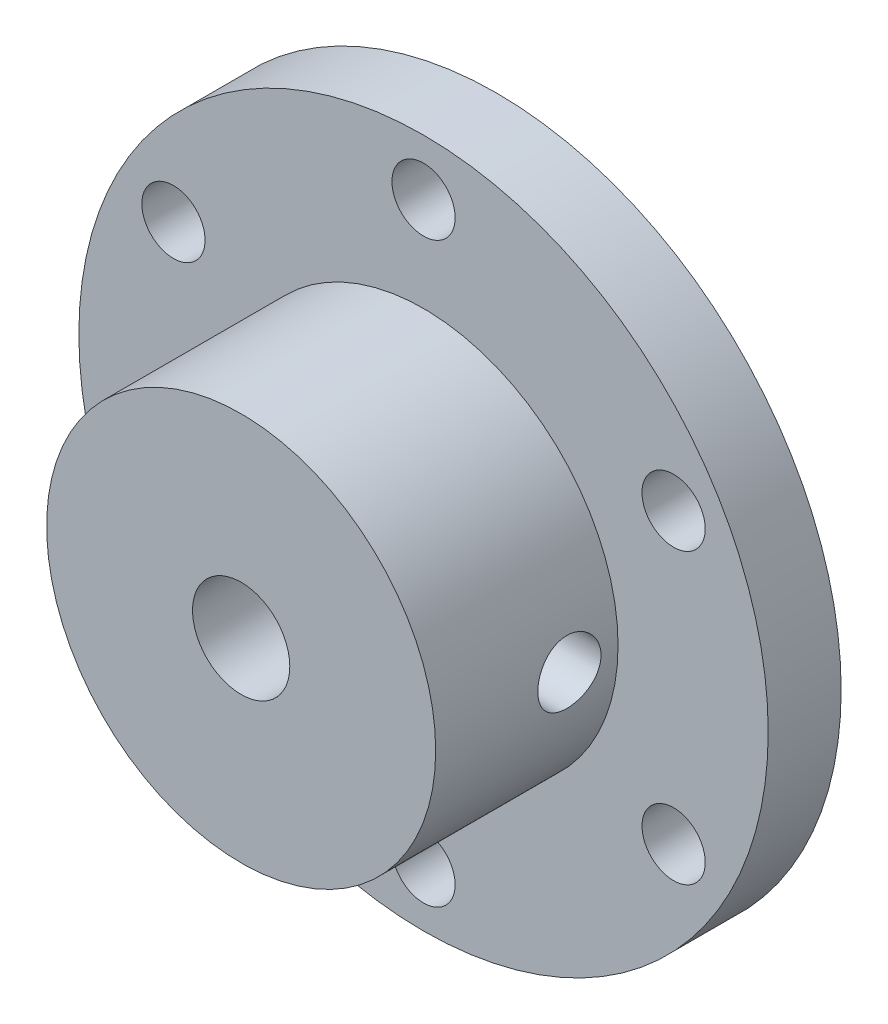
SolidWorks part; units mm, degrees
material "6061 合金"
ref_plane "前基準面" through (0, 0, 0) normal (0, 0, 1) x (1, 0, 0)
ref_plane "上基準面" through (0, 0, 0) normal (0, 1, 0) x (1, 0, 0)
ref_plane "右基準面" through (0, 0, 0) normal (1, 0, 0) x (0, 0, -1)
sketch "草圖1" plane through (0, 0, 0) normal (0, 0, 1) x (1, 0, 0)
  circle A0 centre (0, 0) radius 28.35
  dimension "D1" = 56.7
extrude "填料-伸長1" add sketch "草圖1" along normal blind 6
sketch "草圖2" plane through (0, 0, 6) normal (0, 0, 1) x (1, 0, 0)
  circle A0 centre (0, 0) radius 16
  dimension "D1" = 32
extrude "填料-伸長2" add sketch "草圖2" along normal blind 15
sketch "草圖7" plane through (0, 0, 0) normal (0, 0, -1) x (-1, 0, 0)
  circle A0 centre (0, 0) radius 11
  dimension "D1" = 22
extrude "填料-伸長3" add sketch "草圖7" along normal blind 5
sketch "草圖3" plane through (0, 0, 21) normal (0, 0, 1) x (1, 0, 0)
  circle A0 centre (0, 0) radius 4
  dimension "D1" = 8
extrude "除料-伸長1" cut sketch "草圖3" against normal through all
sketch "草圖4" plane through (0, 0, 6) normal (0, 0, 1) x (1, 0, 0)
  line L0 (0, 0) -> (0, 23.75) construction
  circle A0 centre (0, 23.75) radius 2.6
  dimension "D2" = 5.2
  dimension "D1" = 23.75
extrude "除料-伸長2" cut sketch "草圖4" against normal up to next
pattern_circular "環狀複製排列1" count 6 over 360 about axis through (0, 0, 6) along (0, 0, 1) of "除料-伸長2"
ref_plane "平面1" through (16, 0, 0) normal (1, 0, 0) x (0, 0, -1)
sketch "草圖6" plane through (16, 0, 0) normal (1, 0, 0) x (0, 0, -1)
  line L0 (-21, 0) -> (-6, 0) construction
  line L2 (-21, 16) -> (-21, -16) construction
  line L3 (-6, 28.35) -> (-6, -28.35) construction
  circle A0 centre (-10, 0) radius 2.6
  point P4 (-12.6445, 2.069)
  dimension "D2" = 5.2
  dimension "D1" = 4
extrude "除料-伸長3" cut sketch "草圖6" against normal up to next
ref_axis "基準軸1" through (2.8445, 0, 10) along (1, 0, 0)
